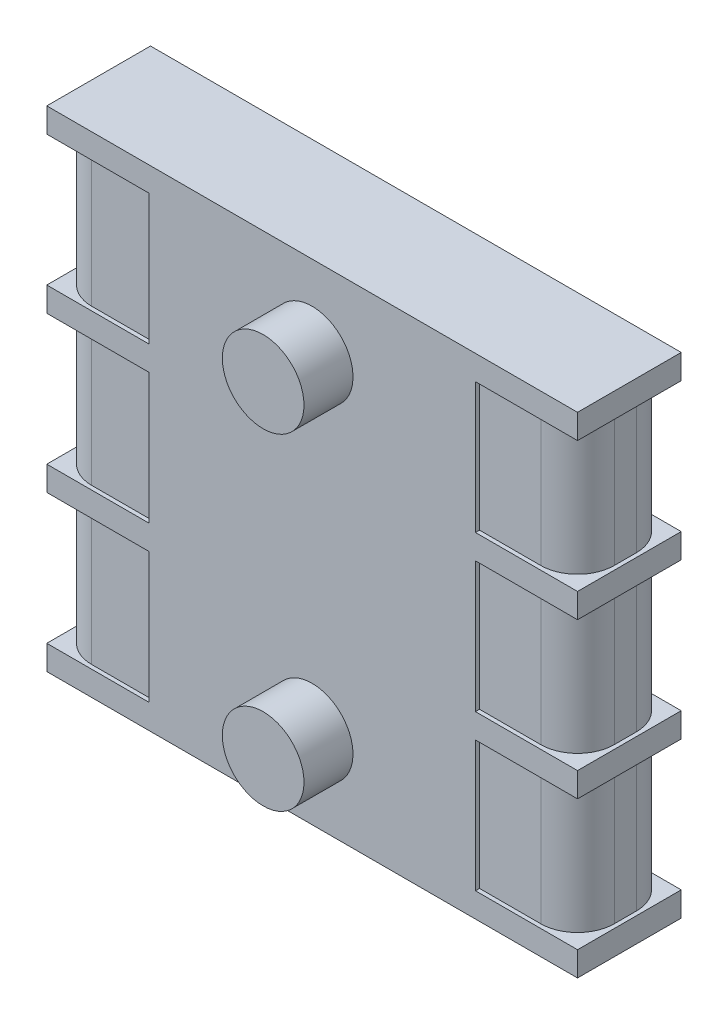
SolidWorks part; units mm, degrees
ref_plane "Front Plane" through (0, 0, 0) normal (0, 0, 1) x (1, 0, 0)
ref_plane "Top Plane" through (0, 0, 0) normal (0, 1, 0) x (1, 0, 0)
ref_plane "Right Plane" through (0, 0, 0) normal (1, 0, 0) x (0, 0, -1)
sketch "Sketch1" plane through (0, 0, 0) normal (0, 1, 0) x (1, 0, 0)
  line L1 (0, 0) -> (6.5, 0)
  line L2 (0, 0) -> (0, 1.27)
  line L3 (0, 1.27) -> (6.5, 1.27)
  line L4 (6.5, 0) -> (6.5, 1.27)
  dimension "D1" = 6.5
  dimension "D2" = 1.27
extrude "Boss-Extrude1" add sketch "Sketch1" along normal blind 0.3
sketch "Sketch2" plane through (0, 0.3, 0) normal (0, 1, 0) x (1, 0, 0)
  line L0 (0.5, 0.2) -> (6, 0.2)
  line L1 (6.3, 0.5) -> (6.3, 0.77)
  line L2 (6, 1.07) -> (0.5, 1.07)
  line L3 (0.2, 0.77) -> (0.2, 0.5)
  line L4 (0, 1.27) -> (0, 0)
  line L5 (0, 0) -> (6.5, 0)
  line L6 (6.5, 0) -> (6.5, 1.27)
  line L7 (6.5, 1.27) -> (0, 1.27)
  line L8 (0, 0.77) -> (0, 0.5) construction
  line L9 (0.5, 0) -> (6, 0) construction
  line L10 (6.5, 0.5) -> (6.5, 0.77) construction
  line L11 (6, 1.27) -> (0.5, 1.27) construction
  line L12 (3.25, 0.2) -> (3.25, 0) construction
  line L13 (1.25, 0.2) -> (1.25, 0)
  line L14 (5.25, 0.2) -> (5.25, 0)
  line L15 (6, 1.22) -> (0.5, 1.22)
  line L16 (6.45, 0.5) -> (6.45, 0.77)
  line L17 (0.5, 0.05) -> (6, 0.05)
  line L18 (0.05, 0.77) -> (0.05, 0.5)
  arc A0 (6.5, 0.77) -> (6, 1.27) centre (6, 0.77) ccw construction
  arc A1 (6, 0) -> (6.5, 0.5) centre (6, 0.5) ccw construction
  arc A2 (0, 0.5) -> (0.5, 0) centre (0.5, 0.5) ccw construction
  arc A3 (0, 0.77) -> (0.5, 1.27) centre (0.5, 0.77) cw construction
  arc A4 (0.2, 0.5) -> (0.5, 0.2) centre (0.5, 0.5) ccw
  arc A5 (6, 0.2) -> (6.3, 0.5) centre (6, 0.5) ccw
  arc A6 (6.3, 0.77) -> (6, 1.07) centre (6, 0.77) ccw
  arc A7 (0.2, 0.77) -> (0.5, 1.07) centre (0.5, 0.77) cw
  arc A8 (0.05, 0.77) -> (0.5, 1.22) centre (0.5, 0.77) cw
  arc A9 (6.45, 0.77) -> (6, 1.22) centre (6, 0.77) ccw
  arc A10 (6, 0.05) -> (6.45, 0.5) centre (6, 0.5) ccw
  arc A11 (0.05, 0.5) -> (0.5, 0.05) centre (0.5, 0.5) ccw
  line M14 (0, 1.27) -> (0, 0)
  line M15 (0, 0) -> (6.5, 0)
  line M16 (6.5, 0) -> (6.5, 1.27)
  line M17 (6.5, 1.27) -> (0, 1.27)
  dimension "D2" = 0.5
  dimension "D1" = 0
  dimension "D3" = 0.2
  dimension "D4" = 2
  dimension "D5" = 2
  dimension "D6" = 0.05
extrude "Boss-Extrude2" add sketch "Sketch2" along normal blind 1.6 contours L3 A7 L2 A6 L1 A5 L0 L14 A1 A0 A3 A2 L13 A4 M15 M16 M17 M14 region at (0.875, 0.3, -0.1349)
extrude "Boss-Extrude3" add sketch "Sketch1<2>" along normal blind 0.3 from surface starting at face at (3.25, 1.9, -0.533)
sketch "Sketch1<2>" plane through (0, 0, 0) normal (0, 1, 0) x (1, 0, 0) same geometry as "Sketch1"
extrude "Boss-Extrude4" add sketch "Sketch2<3>" along normal blind 1.6 from surface contours L3 A7 L2 A6 L1 A5 L0 L14 A1 A0 A3 A2 L13 A4 M15 M16 M17 M14 region at (0.875, 0.3, -0.1349) starting at face at (3.25, 2.2, -0.635)
sketch "Sketch2<3>" plane through (0, 0.3, 0) normal (0, 1, 0) x (1, 0, 0) same geometry as "Sketch2"
extrude "Boss-Extrude5" add sketch "Sketch1<3>" along normal blind 0.3 from surface starting at face at (3.25, 3.8, -0.533)
sketch "Sketch1<3>" plane through (0, 0, 0) normal (0, 1, 0) x (1, 0, 0) same geometry as "Sketch1"
extrude "Boss-Extrude6" add sketch "Sketch2<4>" along normal blind 1.6 from surface contours L3 A7 L2 A6 L1 A5 L0 L14 A1 A0 A3 A2 L13 A4 M15 M16 M17 M14 region at (0.875, 0.3, -0.1349) starting at face at (3.25, 4.1, -0.635)
sketch "Sketch2<4>" plane through (0, 0.3, 0) normal (0, 1, 0) x (1, 0, 0) same geometry as "Sketch2"
extrude "Boss-Extrude7" add sketch "Sketch1<4>" along normal blind 0.3 from surface starting at face at (3.25, 5.7, -0.533)
sketch "Sketch1<4>" plane through (0, 0, 0) normal (0, 1, 0) x (1, 0, 0) same geometry as "Sketch1"
sketch "Sketch3" plane through (0, 0, 0) normal (0, 0, 1) x (1, 0, 0)
  line L1 (1.25, 5.7) -> (5.25, 5.7)
  line L2 (1.25, 5.7) -> (1.25, 0.3)
  line L3 (1.25, 0.3) -> (5.25, 0.3)
  line L4 (5.25, 5.7) -> (5.25, 0.3)
extrude "Boss-Extrude8" add sketch "Sketch3" against normal blind 0.2
sketch "Sketch4" plane through (0, 0, 0) normal (0, 0, 1) x (1, 0, 0)
  line L0 (6.5, 6) -> (0, 6) construction
  line L1 (6.5, 6) -> (0, 6) construction
  line L2 (3.25, 6) -> (3.25, 0) construction
  line L3 (0, 0) -> (6.5, 0) construction
  circle A0 centre (3.25, 5) radius 0.5
  circle A1 centre (3.25, 1) radius 0.5
  dimension "D1" = 1
  dimension "D2" = 4
  dimension "D3" = 1
extrude "Boss-Extrude9" add sketch "Sketch4" along normal blind 0.6
